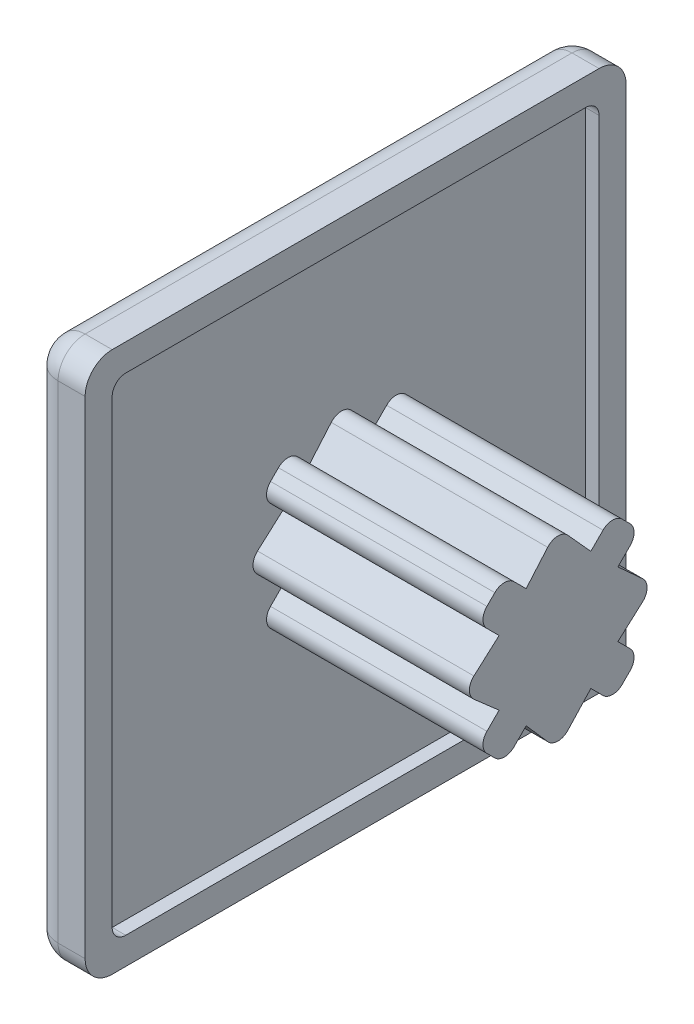
SolidWorks part; units mm, degrees
material "PVC Rigid"
ref_plane "Front Plane" through (0, 0, 0) normal (0, 0, 1) x (1, 0, 0)
ref_plane "Top Plane" through (0, 0, 0) normal (0, 1, 0) x (1, 0, 0)
ref_plane "Right Plane" through (0, 0, 0) normal (1, 0, 0) x (0, 0, -1)
sketch "Sketch2" plane through (0, 0, 0) normal (1, 0, 0) x (0, 0, -1)
  line L1 (0, 0) -> (20, 0)
  line L2 (0, 0) -> (0, 20)
  line L3 (0, 20) -> (20, 20)
  line L4 (20, 0) -> (20, 20)
  dimension "D1" = 20
  dimension "D2" = 20
extrude "Boss-Extrude1" add sketch "Sketch2" along normal blind 2
sketch "Sketch3" plane through (2, 0, 0) normal (1, 0, 0) x (0, 0, -1)
  line L0 (0, 20) -> (0, 0) construction
  line L1 (1, 19) -> (19, 19)
  line L2 (1, 19) -> (1, 1)
  line L3 (1, 1) -> (19, 1)
  line L4 (19, 19) -> (19, 1)
  line L5 (20, 20) -> (0, 20) construction
  line L6 (20, 0) -> (20, 20) construction
  line L7 (0, 0) -> (20, 0) construction
  dimension "D1" = 1
  dimension "D2" = 1
  dimension "D3" = 1
  dimension "D4" = 1
extrude "Cut-Extrude1" cut sketch "Sketch3" against normal blind 0.5
fillet "Fillet1" radius 1 4 edges at (0, 0, -10) (0, 10, -20) (0, 20, -10) (0, 10, 0)
fillet "Fillet2" radius 1 8 edges at (0.2929, 19.7071, -0.2929) (0.2929, 19.7071, -19.7071) (0.2929, 0.2929, -19.7071) (0.2929, 0.2929, -0.2929) (1.5, 20, 0) (1.5, 20, -20) (1.5, 0, -20) (1.5, 0, 0)
fillet "Fillet3" radius 0.5 4 edges at (1.75, 1, -19) (1.75, 19, -19) (1.75, 19, -1) (1.75, 1, -1)
sketch "Sketch4" plane through (1.5, 0, 0) normal (1, 0, 0) x (0, 0, -1)
sketch "Sketch5" plane through (1.5, 0, 0) normal (1, 0, 0) x (0, 0, -1)
  line L0 (13.5, 14.5) -> (5.5, 6.5) construction
  line L1 (14.5, 13.5) -> (6.5, 5.5) construction
  line L2 (10.5, 14.5) -> (14.5, 10.5) construction
  line L3 (12, 13) -> (13, 12)
  line L4 (13, 12) -> (8, 7)
  line L5 (8, 7) -> (7, 8)
  line L6 (7, 8) -> (12, 13)
  line L7 (5.5, 9.5) -> (9.5, 5.5) construction
  line L8 (5.5, 10.5) -> (9.5, 14.5) construction
  line L9 (14.5, 9.5) -> (10.5, 5.5) construction
  line L10 (6.5, 14.5) -> (14.5, 6.5) construction
  line L11 (5.5, 13.5) -> (13.5, 5.5) construction
  line L12 (7, 12) -> (8, 13)
  line L13 (8, 13) -> (13, 8)
  line L14 (13, 8) -> (12, 7)
  line L15 (12, 7) -> (7, 12)
  line L16 (8.8044, 12.1955) -> (9.969, 13.5513)
  line L17 (9.264, 13.5513) -> (10.674, 13.5513)
  line L18 (9.264, 13.5513) -> (9.264, 6.4813)
  line L19 (9.264, 6.4813) -> (10.674, 6.4813)
  line L20 (10.674, 13.5513) -> (10.674, 6.4813)
  line L21 (9.969, 13.5513) -> (11.1956, 12.1955)
  line L22 (8.8044, 12.1955) -> (11.1956, 12.1955)
  line L23 (6.4507, 9.9894) -> (7.8044, 11.1955)
  line L24 (6.4507, 10.6944) -> (13.5207, 10.6944)
  line L25 (6.4507, 10.6944) -> (6.4507, 9.2844)
  line L26 (6.4507, 9.2844) -> (13.5207, 9.2844)
  line L27 (13.5207, 10.6944) -> (13.5207, 9.2844)
  line L28 (7.8044, 11.1955) -> (7.8044, 8.8044)
  line L29 (7.8044, 8.8044) -> (6.4507, 9.9894)
  line L30 (9.969, 6.4813) -> (11.1956, 7.8044)
  line L31 (11.1956, 7.8044) -> (8.8044, 7.8044)
  line L32 (8.8044, 7.8044) -> (9.969, 6.4813)
  line L33 (13.5207, 9.9894) -> (12.1956, 11.1955)
  line L34 (12.1956, 11.1955) -> (12.1956, 8.8044)
  line L35 (12.1956, 8.8044) -> (13.5207, 9.9894)
  circle A0 centre (10, 10) radius 2.5
  point P0 (10, 10)
  dimension "D1" = 7.07
  dimension "D2" = 1.41
  dimension "D3" = 1.41
  dimension "D4" = 7.07
extrude "Boss-Extrude3" add sketch "Sketch5" along normal blind 8 contours A0 L20 L21 L16 L18 | A0 L18 L16 | A0 L21 L20 | L20 A0 L18 L22 | L18 A0 L22 | L22 A0 L20 | L22 L18 L13 L6 L20 | L22 L13 L18 | L22 L20 L6 | L4 A0 L6 L20 L24 | A0 L4 L3 L6 | L13 A0 L15 L24 L18 | A0 L13 L12 L15 | L18 L24 L6 L13 | L13 L24 L20 L6 | L6 L24 L13 | L24 L18 L6 | L24 L15 L6 L18 | L15 L26 L4 L20 L13 L24 L6 L18 | L24 L20 L13 L4 | L18 L6 L15 | L13 L20 L4 | L24 L13 L20 | L28 A0 L24 | L24 A0 L26 L28 | A0 L23 L24 | A0 L24 L23 L29 L26 | L24 L28 L26 L6 L15 | L15 L28 L24 | L26 A0 L28 | L26 L28 L6 | L6 A0 L4 L18 L26 | L6 L26 L18 L15 | L18 L26 L15 | L26 L18 L4 L15 | L31 L18 L4 | L31 L20 L15 L4 L18 | L18 A0 L20 L31 | L15 A0 L13 L26 L20 | L26 L4 L15 L20 | L26 L15 L4 | L4 L26 L20 | L20 L26 L13 L4 | L34 L24 L4 L13 L26 | L34 L4 L24 | L24 A0 L34 | L26 A0 L24 L34 | L34 L26 L13 | L34 A0 L26 | A0 L26 L35 L33 L24 | A0 L35 L26 | A0 L24 L33 | L31 L15 L20 | L20 A0 L31 | L31 A0 L18 | A0 L32 L18 | A0 L18 L32 L30 L20 | A0 L20 L30 | A0 L6 L5 L4 | A0 L15 L14 L13 | A0 L26 L29 region at (1.5, 12.1216, -12.1217) region at (1.5, 11.3296, -11.3234) region at (1.5, 12.4684, -10.8419) region at (1.5, 12.0217, -10.8479) region at (1.5, 12.2702, -10.8566) region at (1.5, 10.8614, -12.0285) region at (1.5, 10.8694, -12.268) region at (1.5, 10.8558, -12.4573) region at (1.5, 11.0752, -10.4315) region at (1.5, 11.7495, -9.982) region at (1.5, 12.8471, -9.9731) region at (1.5, 12.3326, -9.9768) region at (1.5, 9.9938, -11.7495) region at (1.5, 10.4451, -11.0735) region at (1.5, 9.9907, -12.8359) region at (1.5, 9.992, -12.3327) region at (1.5, 10.7962, -10) region at (1.5, 11.0926, -9.5304) region at (1.5, 10.5716, -10.5512) region at (1.5, 12.2632, -9.1041) region at (1.5, 12.0423, -9.1108) region at (1.5, 12.4463, -9.1152) region at (1.5, 9.5418, -11.0793) region at (1.5, 10, -10.7827) region at (1.5, 9.1244, -12.0356) region at (1.5, 9.117, -12.2656) region at (1.5, 9.9946, -9.9844) region at (1.5, 10.5509, -9.4075) region at (1.5, 11.3348, -8.6518) region at (1.5, 12.1216, -7.8784) region at (1.5, 9.4142, -10.5442) region at (1.5, 8.6618, -11.3252) region at (1.5, 9.1294, -12.4498) region at (1.5, 7.8783, -12.1217) region at (1.5, 10, -9.176) region at (1.5, 10.442, -8.9031) region at (1.5, 10.856, -7.5389) region at (1.5, 10.8614, -7.9715) region at (1.5, 10.8694, -7.732) region at (1.5, 8.9169, -10.4303) region at (1.5, 9.1896, -10) region at (1.5, 7.9782, -10.8479) region at (1.5, 7.7297, -10.8566) region at (1.5, 7.536, -10.8417) region at (1.5, 9.5448, -8.897) region at (1.5, 9.9938, -8.2505) region at (1.5, 9.4349, -9.4146) region at (1.5, 9.9907, -7.1536) region at (1.5, 9.992, -7.6673) region at (1.5, 8.2504, -9.982) region at (1.5, 8.8991, -9.5313) region at (1.5, 7.1649, -9.973) region at (1.5, 7.6673, -9.9768) region at (1.5, 8.6567, -8.6501) region at (1.5, 9.1244, -7.9644) region at (1.5, 9.117, -7.7344) region at (1.5, 9.1292, -7.5465) region at (1.5, 7.9576, -9.1108) region at (1.5, 7.7367, -9.1041) region at (1.5, 7.5578, -9.1154)
fillet "Fillet4" radius 0.5 12 edges at (5.5, 9.9894, -6.4507) (5.5, 8, -7) (5.5, 7, -8) (5.5, 6.4813, -9.969) (5.5, 7, -12) (5.5, 8, -13) (5.5, 9.9894, -13.5207) (5.5, 12, -13) (5.5, 13, -12) (5.5, 13.5513, -9.969) (5.5, 13, -8) (5.5, 12, -7)
